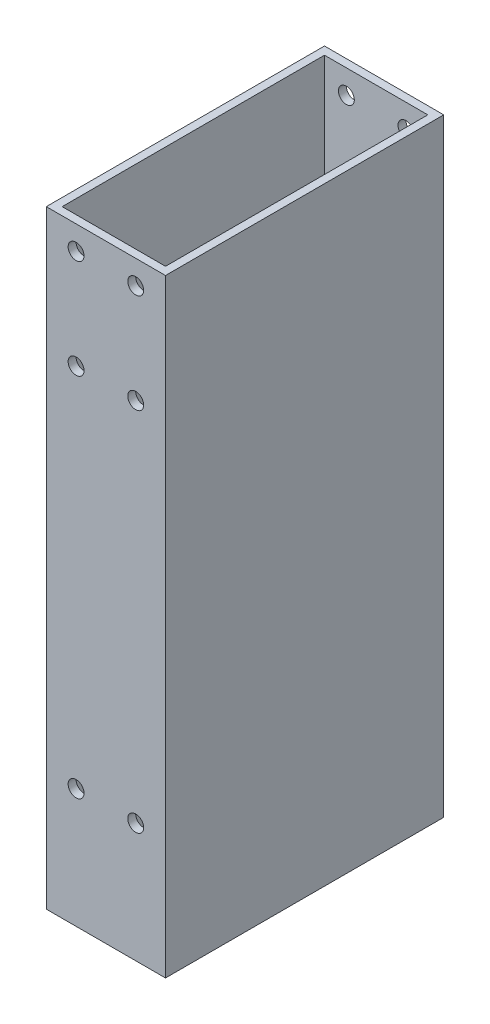
SolidWorks part; units mm, degrees
ref_plane "前视基准面" through (0, 0, 0) normal (0, 0, 1) x (1, 0, 0)
ref_plane "上视基准面" through (0, 0, 0) normal (0, 1, 0) x (1, 0, 0)
ref_plane "右视基准面" through (0, 0, 0) normal (1, 0, 0) x (0, 0, -1)
other "Configuration Table"
sketch "草图1" plane through (0, 0, 0) normal (0, 0, 1) x (1, 0, 0)
  line L1 (15, -383.07) -> (-15, -383.07)
  line L2 (15, -383.07) -> (15, 383.07)
  line L3 (15, 383.07) -> (-15, 383.07)
  line L4 (-15, -383.07) -> (-15, 383.07)
  line L5 (15, -383.07) -> (-15, 383.07) construction
  line L6 (15, 383.07) -> (-15, -383.07) construction
  circle A0 centre (-7.5, 377.0748) radius 2
  circle A1 centre (7.5, 377.0748) radius 2
  circle A2 centre (-7.5, 352.0748) radius 2
  circle A3 centre (7.5, 352.0748) radius 2
  circle A4 centre (7.4999, 260) radius 2 construction
  circle A5 centre (-7.5001, 260) radius 2 construction
  circle A6 centre (7.4999, 260) radius 2
  circle A7 centre (-7.5001, 260) radius 2
  point P0 (0, 0)
  point P8 (0, 0)
  point P9 (-8.5323, 352.1041)
  point P12 (-7.5, 352.0748)
  point P13 (7.5, 352.0748)
  point P16 (-8.5323, 352.0748)
  point P17 (6.2885, 352.1041)
  dimension "D1" = 30
  dimension "D2" = 766.14
extrude "凸台-拉伸2" add sketch "草图1" along normal blind 70
sketch "草图2" plane through (0, -383.07, 0) normal (0, -1, 0) x (1, 0, 0)
  line L0 (-15, 70) -> (-15, 0) construction
  line L1 (-13, 68) -> (13, 68)
  line L2 (-13, 68) -> (-13, 2)
  line L3 (-13, 2) -> (13, 2)
  line L4 (13, 68) -> (13, 2)
  line L5 (-13, 68) -> (13, 2) construction
  line L6 (-13, 2) -> (13, 68) construction
  line L7 (-15, 70) -> (15, 70) construction
  line L8 (15, 70) -> (15, 0) construction
  line L9 (-15, 0) -> (15, 0) construction
  point P0 (0, 35)
  dimension "D1" = 2
  dimension "D2" = 2
  dimension "D3" = 2
  dimension "D4" = 2
extrude "切除-拉伸3" cut sketch "草图2" against normal through all contours L2 L1 L4 L3
sketch "草图3" plane through (0, 0, 70) normal (0, 0, 1) x (1, 0, 0)
  line L0 (-15, 230) -> (15, 230)
  line L1 (-15, 383.07) -> (-15, -383.07) construction
  line L2 (15, -383.07) -> (15, 383.07) construction
  line L3 (15, 383.07) -> (-15, 383.07) construction
  line L4 (-15, 230) -> (-15, -394.9368)
  line L5 (-15, -394.9368) -> (15, -394.9368)
  line L6 (15, -394.9368) -> (15, 230)
  dimension "D1" = 153.07
extrude "切除-拉伸4" cut sketch "草图3" against normal through all
